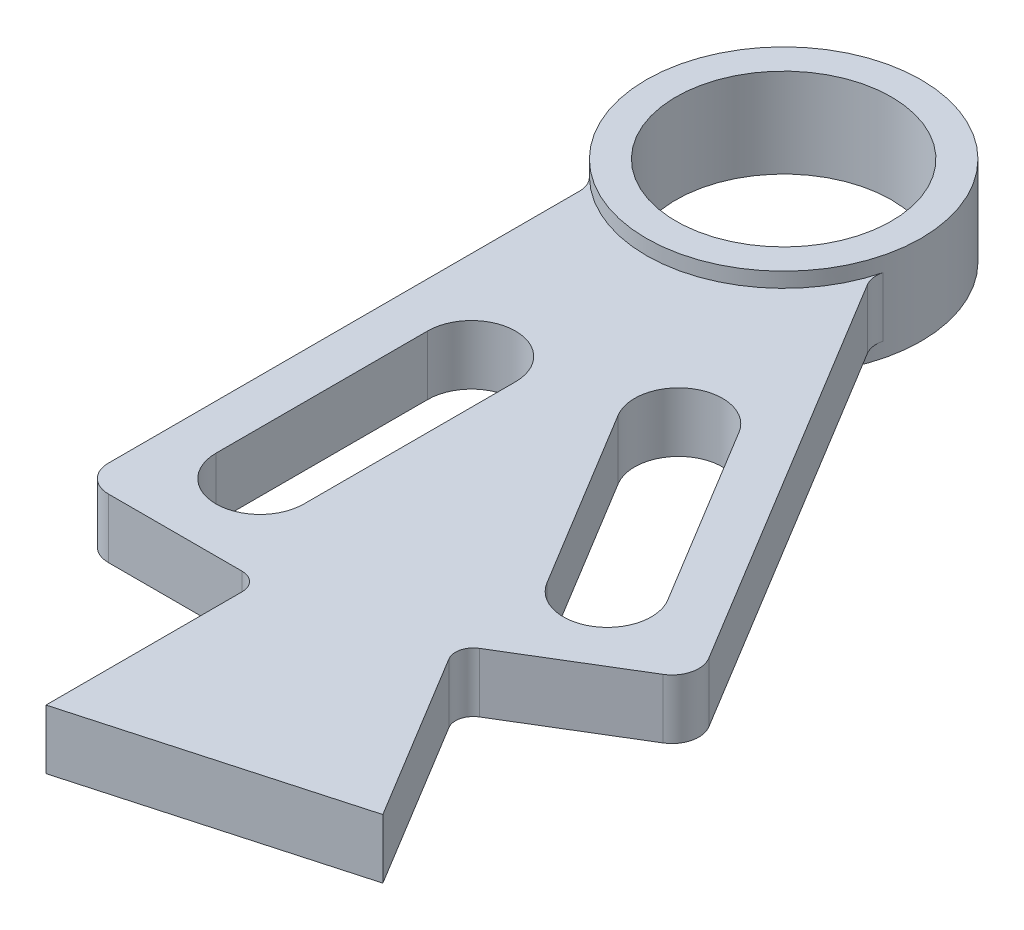
SolidWorks part; units mm, degrees
material "AISI 4130 Steel, annealed at 865C"
ref_plane "Front Plane" through (0, 0, 0) normal (0, 0, 1) x (1, 0, 0)
ref_plane "Top Plane" through (0, 0, 0) normal (0, 1, 0) x (1, 0, 0)
ref_plane "Right Plane" through (0, 0, 0) normal (1, 0, 0) x (0, 0, -1)
sketch "Sketch1" plane through (0, 0, 0) normal (0, 1, 0) x (1, 0, 0)
  line L0 (0, -60.6552) -> (0, -14.6812) construction
  line L1 (31.4453, -51.8676) -> (7.6111, -12.5542) construction
  line L2 (0, -55.9562) -> (0, -33.3502) construction
  line L5 (-4.699, -55.9562) -> (-4.699, -33.3502)
  line L8 (-9.525, -65.4812) -> (9.525, -65.4812)
  line L9 (25.8023, -60.9324) -> (42.0923, -51.0563)
  line L10 (-9.525, -65.4812) -> (-9.525, -11.1719)
  line L11 (42.0923, -51.0563) -> (13.9369, -4.6153)
  line L12 (9.525, -65.4812) -> (9.525, -88.3412)
  line L13 (25.8023, -60.9324) -> (37.6535, -80.4805)
  line L14 (9.525, -88.3412) -> (37.6535, -80.4805)
  line L15 (0, -14.6812) -> (0, 0) construction
  line L16 (0, -65.4812) -> (0, -60.6552) construction
  line L17 (33.9473, -55.9944) -> (31.4453, -51.8676)
  line L18 (4.699, -55.9562) -> (4.699, -33.3502)
  line L19 (17.2897, -28.5185) -> (29.0093, -47.8493) construction
  line L20 (21.3079, -26.0824) -> (33.0275, -45.4132)
  line L21 (13.2715, -30.9546) -> (24.991, -50.2854)
  line L22 (7.6111, -12.5542) -> (0, 0) construction
  line L23 (0, 0) -> (20.5089, -73.3882) construction
  line L25 (188.2624, -310.5296) -> (17.67, -29.1458) construction
  line L27 (0, 0) -> (23.5893, -84.4108) construction
  circle A0 centre (0, 0) radius 11.5062
  circle A1 centre (0, 0) radius 14.6812
  arc A2 (-4.699, -55.9562) -> (4.699, -55.9562) centre (0, -55.9562) ccw
  arc A3 (4.699, -33.3502) -> (-4.699, -33.3502) centre (0, -33.3502) ccw
  arc A4 (21.3079, -26.0824) -> (13.2715, -30.9546) centre (17.2897, -28.5185) ccw
  arc A5 (24.991, -50.2854) -> (33.0275, -45.4132) centre (29.0093, -47.8493) ccw
  point P9 (0, -44.6532)
  point P14 (23.1495, -38.1839)
  point P23 (0, -65.4812)
  point P26 (33.9473, -55.9944)
  point P33 (0, -60.6552)
  point P36 (31.4453, -51.8676)
  point P38 (0, -28.6512)
  dimension "D2" = 29.3624
  dimension "D3" = 50.8
  dimension "D4" = 4.826
  dimension "D6" = 22.86
  dimension "D5" = 4.826
  dimension "D8" = 13.97
  dimension "D9" = 76.2
  dimension "D7" = 9.525
extrude "Bearing extrude" add sketch "Sketch1" along normal mid plane 9.525 contours A1 A0 region at (-5.9782, 0, -12.9529)
extrude "Boss-Extrude2" add sketch "Sketch1<5>" along normal mid plane 6.35 contours A1 L10 L8 L12 L14 L13 L9 L11 A4 A2 region at (13.3713, 0, 47.8474)
sketch "Sketch1<5>" plane through (0, 0, 0) normal (0, 1, 0) x (1, 0, 0) same geometry as "Sketch1"
sketch3d "Tab Point"
  line L0 (20.5089, 0, 73.3882) -> (20.5089, 22.225, 73.3882) construction
  line L1 (0, 0, 0) -> (20.5089, 0, 73.3882) construction
  line L2 (0, 0, 0) -> (23.5893, 0, 84.4108) construction
  dimension "D1" = 22.225
fillet "Fillet1" radius 2.54 2 edges at (13.9369, 0, 4.6153) (-9.525, 0, 11.1719)
fillet "Fillet2" radius 1.905 2 edges at (25.8023, 0, 60.9324) (9.525, 0, 65.4812)
fillet "Fillet3" radius 2.8575 2 edges at (42.0923, 0, 51.0563) (-9.525, 0, 65.4812)
equation "\"Apex_thickness\"= .25"
equation "\"Bearing_diameter\"= .906"
equation "\"A-arm_angle\"= 32.91"
equation "\"D1@Sketch1\"=\"Bearing_diameter\""
equation "\"D1@Boss-Extrude2\"= \"Apex_thickness\""
equation "\"apex slot\"= 1.4"
equation "\"tube diameter\"= 5 / 8"
